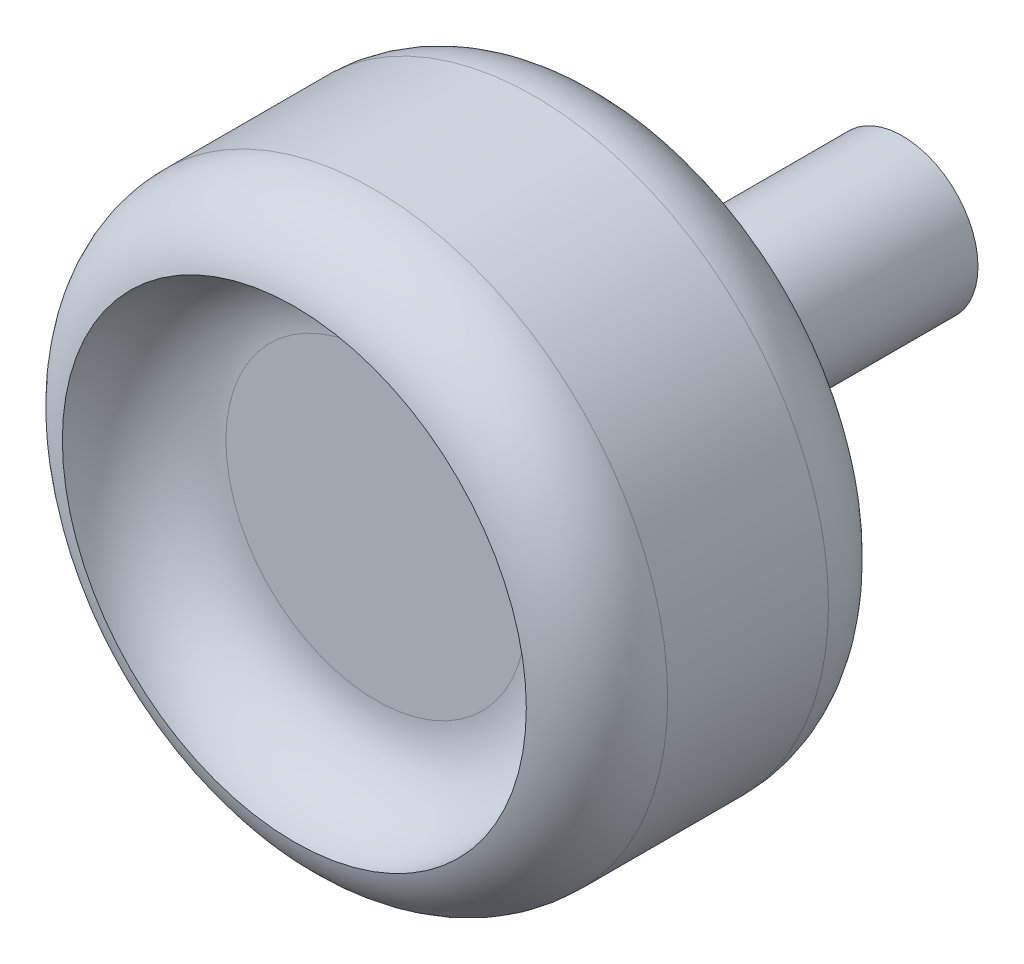
SolidWorks part; units mm, degrees
ref_plane "Front Plane" through (0, 0, 0) normal (0, 0, 1) x (1, 0, 0)
ref_plane "Top Plane" through (0, 0, 0) normal (0, 1, 0) x (1, 0, 0)
ref_plane "Right Plane" through (0, 0, 0) normal (1, 0, 0) x (0, 0, -1)
sketch "Sketch1" plane through (0, 0, 0) normal (0, 0, 1) x (1, 0, 0)
  circle A0 centre (21.7508, -13.8367) radius 2.3454
extrude "Boss-Extrude1" add sketch "Sketch1" along normal blind 8.89
sketch "Sketch2" plane through (0, 0, 8.89) normal (0, 0, 1) x (1, 0, 0)
  circle A0 centre (21.7508, -13.8367) radius 9.1316
extrude "Boss-Extrude2" add sketch "Sketch2" along normal blind 10
sketch "Sketch3" plane through (0, 0, 18.89) normal (0, 0, 1) x (1, 0, 0)
  circle A0 centre (21.7508, -13.8367) radius 7.2056
extrude "Cut-Extrude1" cut sketch "Sketch3" against normal blind 2.54
fillet "Fillet1" radius 2.54 1 edges at (28.9564, -13.8367, 16.35)
fillet "Fillet2" radius 2.54 2 edges at (30.8824, -13.8367, 8.89) (30.8824, -13.8367, 18.89)
